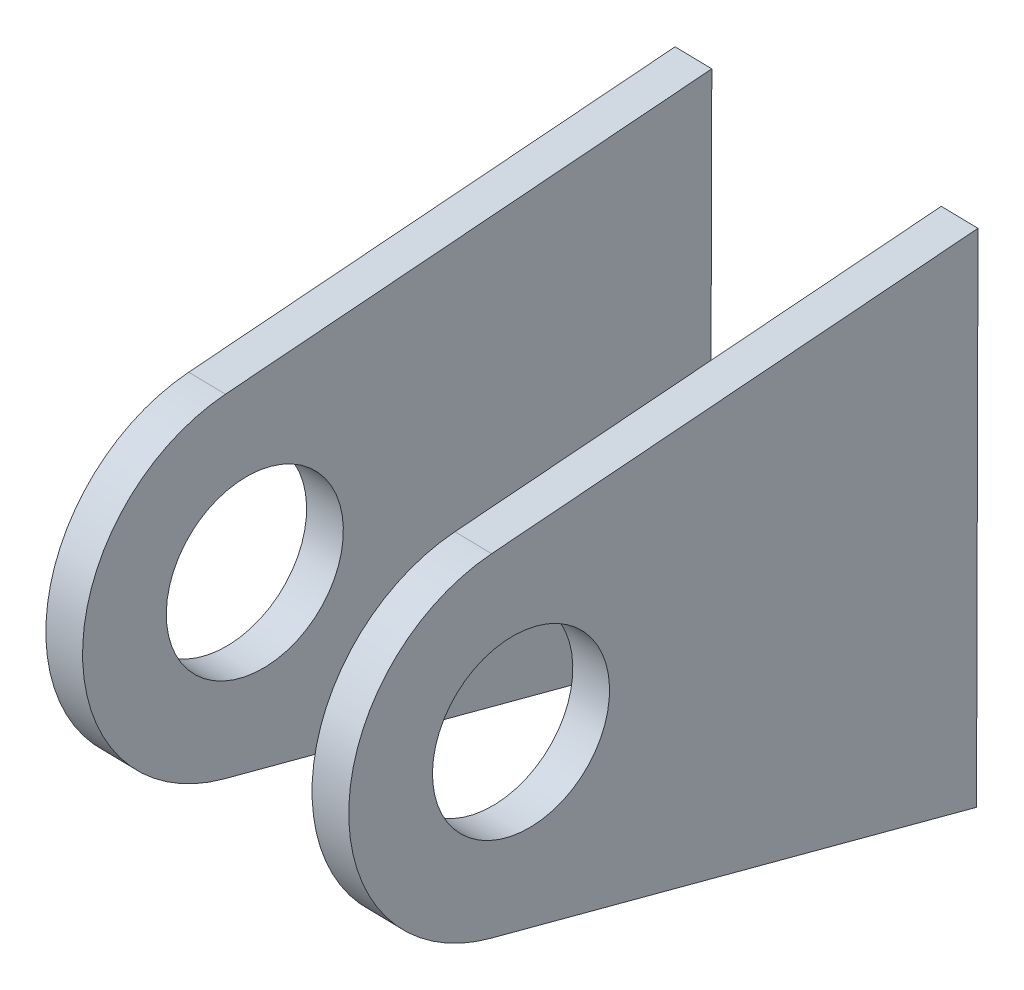
SolidWorks part; units mm, degrees
material "AISI 4130 Steel, normalized at 870C"
ref_plane "Top" through (0, 0, 0) normal (0, 0, 1) x (1, 0, 0)
ref_plane "Right" through (0, 0, 0) normal (0, 1, 0) x (1, 0, 0)
ref_plane "Front" through (0, 0, 0) normal (1, 0, 0) x (0, 0, -1)
sketch "Sketch1" plane through (27.3955, 1.1136, 1.6025) normal (0.9975, 0.0405, 0.0583) x (0.0583, 0.0024, -0.9983)
  line L0 (-116.6685, 501.0602) -> (-117.4461, 482.2488)
  line L1 (-116.5733, 503.3629) -> (-117.402, 483.3144) construction
  line L2 (-117.4461, 482.2488) -> (-135.2227, 486.1465)
  line L3 (-116.6685, 501.0602) -> (-134.7062, 498.6429)
  arc A0 (-134.7062, 498.6429) -> (-135.2227, 486.1465) centre (-133.8627, 492.3491) ccw
  circle A1 centre (-133.8627, 492.3491) radius 3.2639
  dimension "D1" = 6.35
  dimension "D2" = 6.5278
  dimension "D3" = 80
extrude "Boss-Extrude1" add sketch "Sketch1" along normal mid plane 12.573
extrude "Cut-Extrude1" cut sketch "Sketch1<2>" against normal mid plane 9.525
sketch "Sketch1<2>" plane through (27.3955, 1.1136, 1.6025) normal (0.9975, 0.0405, 0.0583) x (0.0583, 0.0024, -0.9983) same geometry as "Sketch1"
